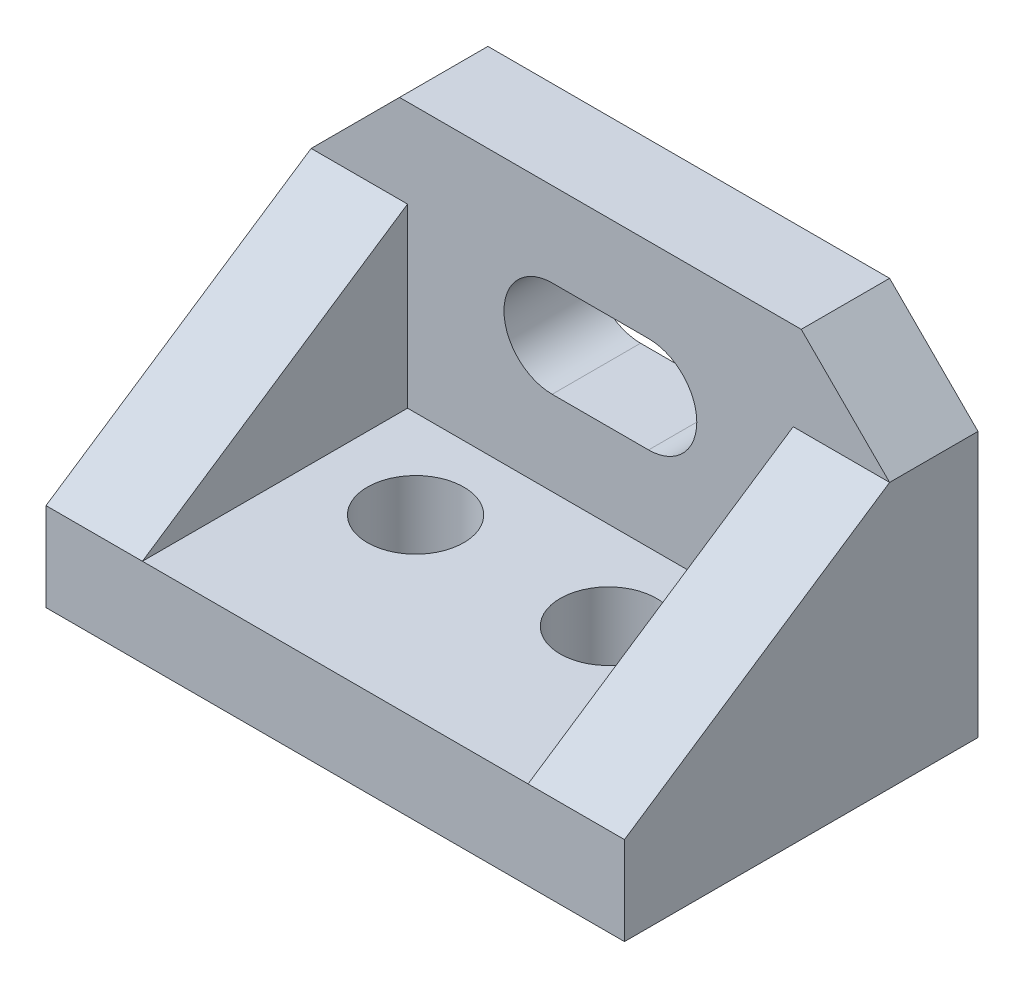
SolidWorks part; units mm, degrees
ref_plane "Front Plane" through (0, 0, 0) normal (0, 0, 1) x (1, 0, 0)
ref_plane "Top Plane" through (0, 0, 0) normal (0, 1, 0) x (1, 0, 0)
ref_plane "Right Plane" through (0, 0, 0) normal (1, 0, 0) x (0, 0, -1)
sketch "Sketch1" plane through (0, 0, 0) normal (1, 0, 0) x (0, 0, -1)
  line L0 (0, 0) -> (0, 34.925)
  line L1 (0, 0) -> (139.7, 0)
  line L4 (139.7, 0) -> (139.7, 139.7)
  line L7 (0, 34.925) -> (104.775, 34.925)
  line L8 (104.775, 34.925) -> (104.775, 139.7)
  line L9 (104.775, 139.7) -> (139.7, 139.7)
  dimension "D1" = 139.7
  dimension "D2" = 139.7
  dimension "D3" = 34.925
  dimension "D4" = 34.925
extrude "Boss-Extrude1" add sketch "Sketch1" against normal blind 228.6
sketch "Sketch4" plane through (0, 0, 0) normal (1, 0, 0) x (0, 0, -1)
  line L0 (0, 34.925) -> (104.775, 104.775)
  line L1 (104.775, 139.7) -> (104.775, 34.925) construction
  line L2 (139.7, 139.7) -> (104.775, 139.7) construction
  line L3 (104.775, 104.775) -> (104.775, 34.925)
  line L4 (104.775, 34.925) -> (0, 34.925)
  dimension "D1" = 34.925
extrude "Boss-Extrude2" add sketch "Sketch4" against normal blind 38.1 contours L4 L0 L3
sketch "Sketch5" plane through (-228.6, 0, 0) normal (-1, 0, 0) x (0, 0, 1)
  line L0 (-104.775, 104.775) -> (0, 34.925)
  line L1 (0, 34.925) -> (-104.775, 34.925)
  line L2 (-104.775, 34.925) -> (-104.775, 104.775)
extrude "Boss-Extrude3" add sketch "Sketch5" against normal blind 38.1 contours L2 L0 L1
sketch "Sketch6" plane through (0, 0, -104.775) normal (0, 0, 1) x (1, 0, 0)
  line L0 (0, 104.775) -> (0, 139.7)
  line L1 (0, 139.7) -> (-34.925, 139.7)
  line L2 (-228.6, 139.7) -> (0, 139.7) construction
  line L3 (-34.925, 139.7) -> (0, 104.775)
  line L4 (-114.3, 165.1) -> (-114.3, -17) construction
  line L5 (-228.6, 139.7) -> (-193.675, 139.7)
  line L6 (-228.6, 104.775) -> (-228.6, 139.7)
  line L7 (-193.675, 139.7) -> (-228.6, 104.775)
  line M10 (0, 104.775) -> (0, 139.7)
  line M11 (0, 139.7) -> (-228.6, 139.7)
  dimension "D1" = 34.925
  dimension "D2" = 34.925
extrude "Cut-Extrude1" cut sketch "Sketch6" against normal blind 34.925 contours L3 M11 M10 | L3 L0 L1 | L5 L7 L6 region at (-11.6417, 128.0583, -104.775)
sketch "Sketch8" plane through (0, 34.925, 0) normal (0, 1, 0) x (1, 0, 0)
  line L0 (-190.5, 0) -> (-38.1, 0) construction
  line L1 (-228.6, 104.775) -> (-228.6, 0) construction
  line L2 (-114.3, 0) -> (-114.3, 104.775) construction
  line L3 (-193.675, 104.775) -> (-34.925, 104.775) construction
  circle A0 centre (-152.4, 69.85) radius 19.05
  circle A1 centre (-76.2, 69.85) radius 19.05
  dimension "D3" = 38.1
  dimension "D1" = 69.85
extrude "Cut-Extrude3" cut sketch "Sketch8" against normal up to surface (34.925 mm away) contours A1 | A0 up to face at (-114.3, 0, -69.85)
sketch "Sketch11" plane through (0, 0, -104.775) normal (0, 0, 1) x (1, 0, 0)
  line L0 (-133.35, 87.3125) -> (-95.25, 87.3125) construction
  line L1 (-133.35, 106.3625) -> (-95.25, 106.3625)
  line L2 (-133.35, 68.2625) -> (-95.25, 68.2625)
  line L3 (0, 34.925) -> (0, 104.775) construction
  line L4 (-193.675, 139.7) -> (-34.925, 139.7) construction
  arc A0 (-133.35, 106.3625) -> (-133.35, 68.2625) centre (-133.35, 87.3125) ccw
  arc A1 (-95.25, 68.2625) -> (-95.25, 106.3625) centre (-95.25, 87.3125) ccw
  point P2 (-114.3, 87.3125)
  point P11 (-114.3, 139.7)
  dimension "D4" = 19.05
  dimension "D1" = 95.25
  dimension "D2" = 38.1
  dimension "D3" = 52.3875
extrude "Cut-Extrude4" cut sketch "Sketch11" against normal up to surface (34.925 mm away) up to face at (-114.3, 81.4917, -139.7)
equation "\"x\"= 2 / 3 * \"l\" - 0.5"
equation "\"D1@Sketch1\"=\"x\""
equation "\"D2@Sketch1\"=\"x\""
equation "\"D3@Sketch1\"=1/4*\"x\""
equation "\"D4@Sketch1\"=1/4*\"x\""
equation "\"l\"=9"
equation "\"D1@Boss-Extrude1\"=\"l\""
equation "\"D1@Sketch4\"=\"x\"/4"
equation "\"D1@Boss-Extrude2\"=\"l\"/6"
equation "\"D1@Boss-Extrude3\"=\"l\"/6"
equation "\"D1@Cut-Extrude1\"=\"x\"/4"
equation "\"D1@Sketch8\"=\"x\"/2"
equation "\"D2@Sketch8\"=\"l\"/3"
equation "\"D3@Sketch8\"=\"l\"/6"
equation "\"D1@Sketch11\"=5/12*\"l\""
equation "\"D2@Sketch11\"=\"l\"/6"
equation "\"D3@Sketch11\"=3/8*\"x\""
equation "\"D4@Sketch11\"=\"l\"/12"
equation "\"D2@Sketch6\"=\"x\"/4"
